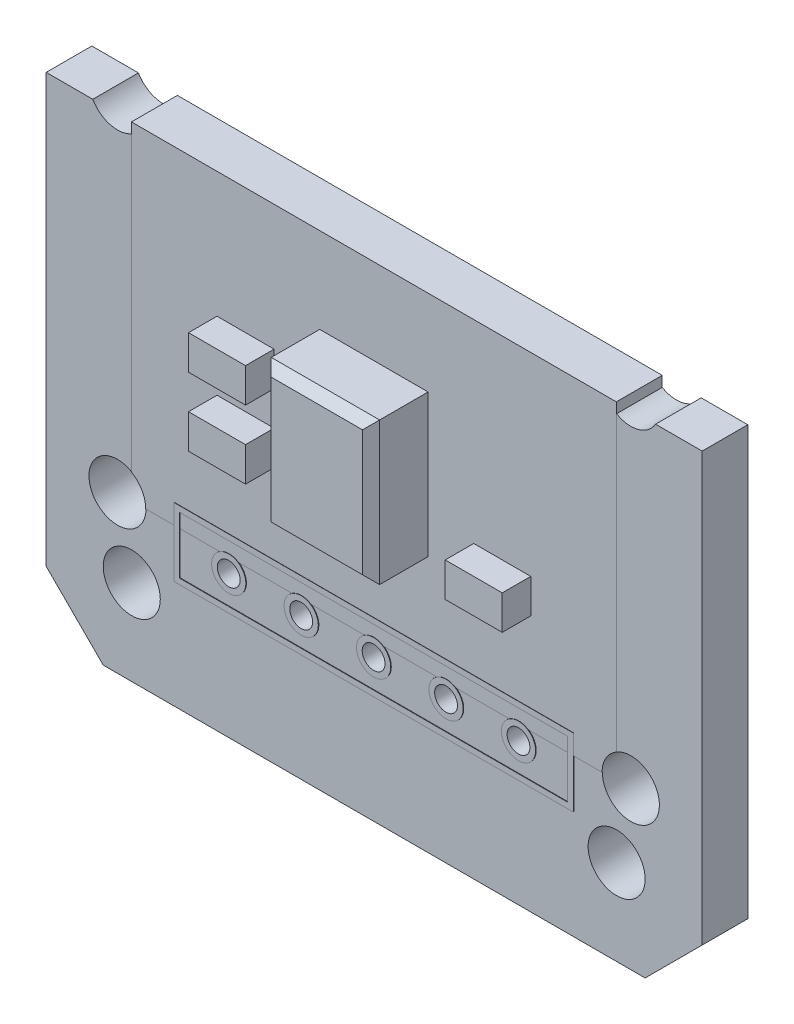
SolidWorks part; units mm, degrees
ref_plane "Front Plane" through (0, 0, 0) normal (0, 0, 1) x (1, 0, 0)
ref_plane "Top Plane" through (0, 0, 0) normal (0, 1, 0) x (1, 0, 0)
ref_plane "Right Plane" through (0, 0, 0) normal (1, 0, 0) x (0, 0, -1)
sketch "Sketch1" plane through (0, 0, 0) normal (0, 0, 1) x (1, 0, 0)
  line L0 (-11.5, 9.5) -> (-9.5, 11.5)
  line L1 (-9.5, -11.5) -> (9.5, -11.5)
  line L2 (-11.5, -9.5) -> (-11.5, 9.5)
  line L3 (-9.5, 11.5) -> (9.5, 11.5)
  line L4 (11.5, -9.5) -> (11.5, 9.5)
  line L7 (9.5, 11.5) -> (11.5, 9.5)
  line L8 (9.5, -11.5) -> (11.5, -9.5)
  line L9 (-11.5, -9.5) -> (-9.5, -11.5)
  line L11 (-9, -6) -> (9, -6) construction
  line L12 (-9, -6) -> (-9, 6) construction
  line L13 (-9, 6) -> (9, 6) construction
  line L14 (9, -6) -> (9, 6) construction
  circle A0 centre (-9, 6) radius 1
  circle A1 centre (9, 6) radius 1
  circle A2 centre (-9, -6) radius 1
  circle A3 centre (9, -6) radius 1
  circle A4 centre (8.5, -8.5) radius 1
  circle A5 centre (-8.5, -8.5) radius 1
  point P0 (0, 0)
  point P1 (0, 11.5)
  point P4 (0, -6)
  point P14 (9, 0)
  point P20 (0, 0)
  point P22 (0, 0)
  dimension "D4" = 2
  dimension "D9" = 3
  dimension "D10" = 3
  dimension "D11" = 3
  dimension "D12" = 2
  dimension "D1" = 23
  dimension "D2" = 23
  dimension "D3" = 2
  dimension "D5" = 2
  dimension "D6" = 11.5
  dimension "D7" = 12
  dimension "D8" = 2.5
extrude "Boss-Extrude1" add sketch "Sketch1" along normal blind 1.6
sketch "Sketch2" plane through (0, 0, 0) normal (0, 0, 1) x (1, 0, 0)
  line L0 (11.5, -9.5) -> (11.5, 9.5) construction
  line L1 (-8.5, -6) -> (8.5, -6)
  line L2 (-8.5, -6) -> (-8.5, 6)
  line L3 (-8.5, 6) -> (8.5, 6)
  line L4 (8.5, -6) -> (8.5, 6)
  line L5 (-8.5, -6) -> (8.5, 6) construction
  line L6 (-8.5, 6) -> (8.5, -6) construction
  line L7 (-9.5, -11.5) -> (9.5, -11.5) construction
  point P0 (0, 0)
  dimension "D1" = 3
  dimension "D2" = 5.5
extrude "Boss-Extrude2" add sketch "Sketch2" along normal blind 1.61
sketch "Sketch3" plane through (0, 0, 0) normal (0, 0, 1) x (1, 0, 0)
  line L0 (0, -5.3) -> (0, -7.7) construction
  line L1 (-7, -7.7) -> (7, -7.7)
  line L2 (-7, -7.7) -> (-7, -5.3)
  line L3 (-7, -5.3) -> (7, -5.3)
  line L4 (7, -7.7) -> (7, -5.3)
  line L5 (-7, -7.7) -> (7, -5.3) construction
  line L6 (-7, -5.3) -> (7, -7.7) construction
  line L7 (-6.8, -5.5) -> (6.8, -5.5)
  line L8 (6.8, -7.5) -> (6.8, -5.5)
  line L9 (-6.8, -7.5) -> (6.8, -7.5)
  line L10 (-6.8, -7.5) -> (-6.8, -5.5)
  circle A0 centre (0, -6.5) radius 0.6
  circle A1 centre (2.54, -6.5) radius 0.6
  circle A2 centre (5.08, -6.5) radius 0.6
  circle A3 centre (-5.08, -6.5) radius 0.6
  circle A4 centre (-2.54, -6.5) radius 0.6
  circle A5 centre (-5.08, -6.5) radius 0.4
  circle A6 centre (-2.54, -6.5) radius 0.4
  circle A7 centre (0, -6.5) radius 0.4
  circle A8 centre (2.54, -6.5) radius 0.4
  circle A9 centre (5.08, -6.5) radius 0.4
  point P0 (0, -6.5)
  dimension "D6" = 1.2
  dimension "D1" = 14
  dimension "D2" = 2.4
  dimension "D3" = 6.5
  dimension "D4" = 2.54
  dimension "D5" = 2.54
  dimension "D7" = 0.2
extrude "Boss-Extrude3" add sketch "Sketch3" along normal blind 1.62 contours A1 A8 | A2 A9 | A0 A7 | A4 A6 | A3 A5 | L1 L4 L3 L2 L9 L10 L7 L8 region at (-6.858, -6.5, 0) region at (-0.583, -6.5, 0) region at (1.957, -6.5, 0) region at (4.497, -6.5, 0) region at (-5.663, -6.5, 0) region at (-3.123, -6.5, 0)
extrude "Cut-Extrude1" cut sketch "Sketch3<3>" along normal blind 2.62 contours A5 | A6 | A7 | A8 | A9 region at (-5.08, -6.5, 0) region at (-2.54, -6.5, 0) region at (0, -6.5, 0) region at (2.54, -6.5, 0) region at (5.08, -6.5, 0)
sketch "Sketch3<3>" plane through (0, 0, 0) normal (0, 0, 1) x (1, 0, 0) same geometry as "Sketch3"
sketch "Sketch4" plane through (0, 0, 0) normal (0, 0, 1) x (1, 0, 0)
  line L1 (-1.9, -2.5) -> (1.9, -2.5)
  line L2 (-1.9, -2.5) -> (-1.9, 2.5)
  line L3 (-1.9, 2.5) -> (1.9, 2.5)
  line L4 (1.9, -2.5) -> (1.9, 2.5)
  line L5 (-1.9, -2.5) -> (1.9, 2.5) construction
  line L6 (-1.9, 2.5) -> (1.9, -2.5) construction
  point P0 (0, 0)
  dimension "D1" = 5
  dimension "D2" = 3.8
extrude "Boss-Extrude4" add sketch "Sketch4" along normal blind 2 from surface starting at face at (0, -2.825, 1.61)
sketch "Sketch5" plane through (0, 0, 0) normal (0, 0, 1) x (1, 0, 0)
  line L1 (-5.5001, -1.3) -> (-3.5001, -1.3)
  line L2 (-5.5001, -1.3) -> (-5.5001, -2.5)
  line L3 (-5.5001, -2.5) -> (-3.5001, -2.5)
  line L4 (-3.5001, -1.3) -> (-3.5001, -2.5)
  line L5 (-5.5001, -1.3) -> (-3.5001, -2.5) construction
  line L6 (-5.5001, -2.5) -> (-3.5001, -1.3) construction
  line L7 (-5.5, 1.1) -> (-3.5, 1.1)
  line L8 (-5.5, 1.1) -> (-5.5, -0.1)
  line L9 (-5.5, -0.1) -> (-3.5, -0.1)
  line L10 (-3.5, 1.1) -> (-3.5, -0.1)
  line L11 (-5.5, 1.1) -> (-3.5, -0.1) construction
  line L12 (-5.5, -0.1) -> (-3.5, 1.1) construction
  line L13 (3.5, -1.3) -> (5.5, -1.3)
  line L14 (3.5, -1.3) -> (3.5, -2.5)
  line L15 (3.5, -2.5) -> (5.5, -2.5)
  line L16 (5.5, -1.3) -> (5.5, -2.5)
  line L17 (3.5, -1.3) -> (5.5, -2.5) construction
  line L18 (3.5, -2.5) -> (5.5, -1.3) construction
  line L19 (1.9, -2.5) -> (1.9, 2.5) construction
  line L20 (-1.9, 2.5) -> (-1.9, -2.5) construction
  line L21 (-1.9, -2.5) -> (1.9, -2.5) construction
  point P0 (-4.5001, -1.9)
  point P5 (-4.5, 0.5)
  point P10 (4.5, -1.9)
  dimension "D1" = 1.2
  dimension "D2" = 2
  dimension "D3" = 1.6
  dimension "D4" = 1.6
  dimension "D5" = 1.2
extrude "Boss-Extrude5" add sketch "Sketch5" along normal blind 1 from surface starting at face at (0, -2.825, 1.61)
chamfer "Chamfer1" distance 0.3 angle 45 4 edges at (0, -2.5, 3.61) (-1.9, 0, 3.61) (0, 2.5, 3.61) (1.9, 0, 3.61)
sketch "Sketch6" plane through (0, 0, 0) normal (0, 0, 1) x (1, 0, 0)
  line L0 (11.5, -9.5) -> (11.5, 9.5) construction
  line L1 (11.5, 5.5) -> (-11.5, 5.5)
  line L2 (11.5, 5.5) -> (11.5, 11.5)
  line L3 (11.5, 11.5) -> (-11.5, 11.5)
  line L4 (-11.5, 5.5) -> (-11.5, 11.5)
  line L5 (-11.5, 9.5) -> (-11.5, -9.5) construction
  line L6 (9.5, 11.5) -> (-9.5, 11.5) construction
  circle A0 centre (9, -6) radius 1
  circle A1 centre (-9, -6) radius 1
  dimension "D1" = 6
extrude "Cut-Extrude2" cut sketch "Sketch6" along normal blind 2
